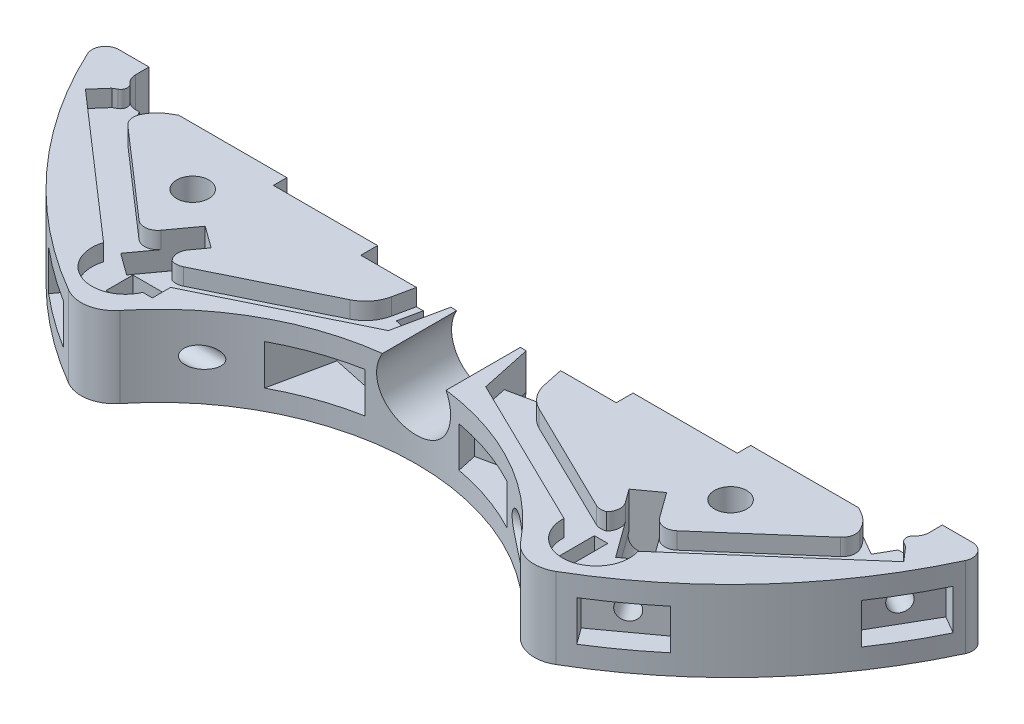
SolidWorks part; units mm, degrees
material "ABS"
ref_plane "Front Plane" through (0, 0, 0) normal (0, 0, 1) x (1, 0, 0)
ref_plane "Top Plane" through (0, 0, 0) normal (0, 1, 0) x (1, 0, 0)
ref_plane "Right Plane" through (0, 0, 0) normal (1, 0, 0) x (0, 0, -1)
sketch "Sketch1" plane through (0, 0, 0) normal (0, 1, 0) x (1, 0, 0)
  line L0 (0, -85) -> (-32.2211, -64.3879) construction
  line L1 (0, -85) -> (0, 0) construction
  arc A0 (36.2245, -62.2237) -> (-36.2245, -62.2237) centre (0, 0) ccw
  arc A1 (29.8119, -61.0352) -> (-29.8119, -61.0352) centre (0, -85) ccw
  arc A2 (36.2245, -62.2237) -> (29.8119, -61.0352) centre (33.7089, -57.9026) cw
  arc A3 (-29.8119, -61.0352) -> (-36.2245, -62.2237) centre (-33.7089, -57.9026) cw
  dimension "D1" = 144
  dimension "D2" = 76.5
  dimension "D4" = 5
  dimension "D3" = 85
extrude "Boss-Extrude1" add sketch "Sketch1" along normal mid plane 12
sketch "solenoid placement" plane through (0, 6, 0) normal (0, 1, 0) x (1, 0, 0)
  line L0 (0, 0) -> (0, -36) construction
  line L5 (-19, -36) -> (19, -36)
  line L7 (19, -36) -> (19, 28)
  line L9 (19, 28) -> (-19, 28)
  line L11 (-19, 28) -> (-19, -36)
  circle A1 centre (0, 0) radius 72 construction
  arc A2 (36.2245, -62.2237) -> (-36.2245, -62.2237) centre (0, 0) ccw construction
  point P7 (0, 28)
  dimension "D1" = 38
  dimension "D2" = 64
  dimension "D3" = 36
extrude "Cut-Extrude1" cut sketch "solenoid placement" against normal through all
sketch "Sketch6" plane through (0, 6, 0) normal (0, 1, 0) x (1, 0, 0)
  line L0 (0, 0) -> (0, -46.75) construction
  arc A0 (29.8119, -61.0352) -> (-29.8119, -61.0352) centre (0, -85) ccw construction
  circle A1 centre (40, -40) radius 2.4
  circle A4 centre (-40, -40) radius 2.4
  dimension "D1" = 4.8
  dimension "D2" = 40
  dimension "D3" = 40
extrude "Cut-Extrude6" cut sketch "Sketch6" against normal through all
sketch "Sketch3" plane through (0, 6, 0) normal (0, 1, 0) x (1, 0, 0)
  line L0 (-72, -27.5) -> (-59, -27.5)
  line L1 (-59, -31.5) -> (59, -31.5)
  line L2 (-72, -27.5) -> (-72, 31.5)
  line L3 (-59, -27.5) -> (-59, -31.5)
  line L4 (72, -27.5) -> (72, 31.5)
  line L5 (-72, 31.5) -> (72, 31.5) construction
  line L6 (0, 31.5) -> (0, -31.5) construction
  line L7 (59, -27.5) -> (59, -31.5)
  line L8 (-72, 31.5) -> (-72, 72)
  line L9 (72, -27.5) -> (59, -27.5)
  line L10 (-72, 72) -> (72, 72)
  line L11 (72, 31.5) -> (72, 72)
  arc A0 (36.2245, -62.2237) -> (-36.2245, -62.2237) centre (0, 0) ccw construction
  arc A1 (36.2245, -62.2237) -> (-36.2245, -62.2237) centre (0, 0) ccw construction
  point P0 (0, 0)
  dimension "D2" = 4
  dimension "D1" = 63
  dimension "D3" = 13
extrude "Cut-Extrude3" cut sketch "Sketch3" against normal through all
fillet "Fillet1" radius 2 4 edges at (66.5413, 0, 27.5) (59, 0, 31.5) (-66.5413, 0, 27.5) (-59, 0, 31.5)
sketch "Sketch8" plane through (0, 0, 0) normal (0, 1, 0) x (1, 0, 0)
  line L0 (0, 0) -> (62.3538, -36) construction
  line L1 (0, 0) -> (42.3205, -58.2492) construction
  line L2 (0, 0) -> (14.9696, -70.4266) construction
  line L3 (0, 0) -> (-14.9696, -70.4266) construction
  line L4 (-42.3205, -58.2492) -> (0, 0) construction
  line L5 (0, 0) -> (-62.3538, -36) construction
  line L6 (0, 0) -> (0, -72) construction
  arc A0 (-62.3538, -36) -> (-42.3205, -58.2492) centre (0, 0) ccw construction
  arc A1 (62.3538, -36) -> (42.3205, -58.2492) centre (0, 0) cw construction
  arc A2 (14.9696, -70.4266) -> (42.3205, -58.2492) centre (0, 0) ccw construction
  arc A3 (14.9696, -70.4266) -> (-14.9696, -70.4266) centre (0, 0) cw construction
  arc A4 (-14.9696, -70.4266) -> (-42.3205, -58.2492) centre (0, 0) cw construction
  arc A5 (36.2245, -62.2237) -> (65.294, -30.3429) centre (0, 0) ccw construction
  dimension "D1" = 120
sketch "Sketch9" plane through (0, 0, 0) normal (0, 1, 0) x (1, 0, 0)
  line L0 (0, 0) -> (-59.7033, -40.2432) construction
  line L1 (0, 0) -> (-64.7033, -31.583) construction
  line L2 (-64.7033, -31.583) -> (-59.7033, -40.2432) construction
  line L3 (-64.7033, -31.583) -> (-62.1052, -30.083)
  line L4 (-62.1052, -30.083) -> (-57.1052, -38.7432)
  line L5 (-57.1052, -38.7432) -> (-59.7033, -40.2432)
  line L6 (-46.2635, -55.1697) -> (-44.5001, -52.7426)
  line L7 (-44.5001, -52.7426) -> (-36.4099, -58.6205)
  line L8 (-36.4099, -58.6205) -> (-38.1733, -61.0475)
  line L9 (0, 0) -> (-38.1733, -61.0475) construction
  line L10 (0, 0) -> (-46.2635, -55.1697) construction
  line L11 (-46.2635, -55.1697) -> (-38.1733, -61.0475) construction
  line L12 (-19.8242, -69.217) -> (-19.2005, -66.2826) [skipped]
  line L13 (-19.2005, -66.2826) -> (-9.419, -68.3617) [skipped]
  line L14 (-9.419, -68.3617) -> (-10.0428, -71.2962) [skipped]
  line L15 (0, 0) -> (-10.0428, -71.2962) construction
  line L16 (0, 0) -> (-19.8242, -69.217) construction
  line L17 (-19.8242, -69.217) -> (-10.0428, -71.2962) construction
  line L18 (10.0428, -71.2962) -> (9.419, -68.3617) [skipped]
  line L19 (9.419, -68.3617) -> (19.2005, -66.2826) [skipped]
  line L20 (19.2005, -66.2826) -> (19.8242, -69.217) [skipped]
  line L21 (0, 0) -> (19.8242, -69.217) construction
  line L22 (0, 0) -> (10.0428, -71.2962) construction
  line L23 (10.0428, -71.2962) -> (19.8242, -69.217) construction
  line L24 (38.1733, -61.0475) -> (36.4099, -58.6205)
  line L25 (36.4099, -58.6205) -> (44.5001, -52.7426)
  line L26 (44.5001, -52.7426) -> (46.2635, -55.1697)
  line L27 (0, 0) -> (46.2635, -55.1697) construction
  line L28 (0, 0) -> (38.1733, -61.0475) construction
  line L29 (38.1733, -61.0475) -> (46.2635, -55.1697) construction
  line L30 (59.7033, -40.2432) -> (57.1052, -38.7432)
  line L31 (57.1052, -38.7432) -> (62.1052, -30.083)
  line L32 (62.1052, -30.083) -> (64.7033, -31.583)
  line L33 (0, 0) -> (64.7033, -31.583) construction
  line L34 (0, 0) -> (59.7033, -40.2432) construction
  line L35 (59.7033, -40.2432) -> (64.7033, -31.583) construction
  arc A0 (-59.7033, -40.2432) -> (-64.7033, -31.583) centre (0, 0) cw
  arc A1 (-62.3538, -36) -> (-42.3205, -58.2492) centre (0, 0) ccw construction
  arc A2 (-38.1733, -61.0475) -> (-46.2635, -55.1697) centre (0, 0) cw
  arc A3 (-10.0428, -71.2962) -> (-19.8242, -69.217) centre (0, 0) cw [skipped]
  arc A4 (19.8242, -69.217) -> (10.0428, -71.2962) centre (0, 0) cw [skipped]
  arc A5 (46.2635, -55.1697) -> (38.1733, -61.0475) centre (0, 0) cw
  arc A6 (64.7033, -31.583) -> (59.7033, -40.2432) centre (0, 0) cw
  point P8 (-62.3538, -36)
  point P12 (62.3538, -36)
  point P34 (0, 0)
  dimension "D1" = 10
  dimension "D2" = 3
  dimension "D3" = 6
extrude "Cut-Extrude7" cut sketch "Sketch9" against normal mid plane 6
sketch "Sketch11" plane through (0, 0, 36) normal (0, 0, -1) x (-1, 0, 0)
  line L0 (0, -6) -> (0, 3.2) construction
  line L1 (19, -6) -> (-19, -6) construction
  circle A0 centre (0, 3.2) radius 5.5
  dimension "D2" = 11
  dimension "D1" = 9.2
extrude "Cut-Extrude8" cut sketch "Sketch11" against normal through all
sketch "Sketch12" plane through (0, 6, 0) normal (0, 1, 0) x (1, 0, 0)
  line L1 (-34.5, 33.5) -> (34.5, 33.5)
  line L2 (-34.5, 33.5) -> (-34.5, -33.5)
  line L3 (-34.5, -33.5) -> (34.5, -33.5)
  line L4 (34.5, 33.5) -> (34.5, -33.5)
  line L5 (-34.5, 33.5) -> (34.5, -33.5) construction
  line L6 (-34.5, -33.5) -> (34.5, 33.5) construction
  point P0 (0, 0)
  dimension "D1" = 69
  dimension "D2" = 67
extrude "Cut-Extrude9" cut sketch "Sketch12" against normal through all
sketch "Sketch13" plane through (0, 6, 0) normal (0, 1, 0) x (1, 0, 0)
  line L0 (0, 0) -> (0, -97.3817) construction
  circle A0 centre (-35, -55) radius 5
  circle A1 centre (35, -55) radius 5
  dimension "D3" = 10
  dimension "D1" = 35
  dimension "D2" = 55
extrude "Cut-Extrude10" cut sketch "Sketch13" against normal blind 2.5
sketch "Sketch14" plane through (0, 0, 0) normal (0, 1, 0) x (1, 0, 0)
  line L0 (16.1653, -42.3838) -> (6.3839, -44.463)
  line L1 (16.1653, -42.3838) -> (16.7891, -45.3183)
  line L2 (6.3839, -44.463) -> (7.0076, -47.3974)
  line L3 (16.7891, -45.3183) -> (7.0076, -47.3974) construction
  line L4 (0, 0) -> (14.9696, -70.4266) construction
  line L5 (16.7891, -45.3183) -> (7.0076, -47.3974) construction
  line L6 (16.7891, -45.3183) -> (18.0563, -51.2801)
  line L7 (7.0076, -47.3974) -> (8.2748, -53.3592)
  line L8 (18.0563, -51.2801) -> (8.2748, -53.3592)
  line L9 (0, 0) -> (0, -72) construction
  line L10 (-16.7891, -45.3183) -> (-7.0076, -47.3974) construction
  line L11 (-16.7891, -45.3183) -> (-7.0076, -47.3974) construction
  line L12 (-18.0563, -51.2801) -> (-8.2748, -53.3592)
  line L13 (-7.0076, -47.3974) -> (-8.2748, -53.3592)
  line L14 (-16.7891, -45.3183) -> (-18.0563, -51.2801)
  line L15 (-6.3839, -44.463) -> (-7.0076, -47.3974)
  line L16 (-16.1653, -42.3838) -> (-16.7891, -45.3183)
  line L17 (-16.1653, -42.3838) -> (-6.3839, -44.463)
  arc A0 (29.8119, -61.0352) -> (4.7339, -47.0441) centre (0, -85) ccw construction
  dimension "D1" = 10
  dimension "D2" = 3
  dimension "D3" = 3
extrude "Cut-Extrude11" cut sketch "Sketch14" against normal mid plane 6
sketch "Sketch15" plane through (59.6052, 0, 34.4131) normal (0.866, 0, 0.5) x (0.5, 0, -0.866)
  circle A0 centre (0, 0) radius 1.55
  dimension "D1" = 3.1
extrude "Cut-Extrude12" cut sketch "Sketch15" against normal blind 4.2
sketch "Sketch16" plane through (55.9679, 0, 32.3131) normal (0.866, 0, 0.5) x (0.5, 0, -0.866)
  circle A0 centre (0, 0) radius 2.1
  dimension "D1" = 4.2
extrude "Cut-Extrude13" cut sketch "Sketch16" against normal blind 9
sketch "Sketch17" plane through (55.9679, 0, 32.3131) normal (-0.866, 0, -0.5) x (-0.5, 0, 0.866)
  line L1 (-2, 0) -> (2, 0)
  line L2 (-2, 0) -> (-2, 7.9151)
  line L3 (-2, 7.9151) -> (2, 7.9151)
  line L4 (2, 0) -> (2, 7.9151)
  point P0 (0, 0)
  dimension "D1" = 4
extrude "Cut-Extrude14" cut sketch "Sketch17" along normal blind 9
pattern_circular "CirPattern1" count 6 over 120 about axis through (0, 6, 0) along (0, -1, 0) of "Cut-Extrude12", "Cut-Extrude13", "Cut-Extrude14"
sketch "Sketch18" plane through (9.3183, 0, 43.8392) normal (0.2079, 0, 0.9781) x (0.9781, 0, -0.2079)
  circle A0 centre (0, 0) radius 1.55
  dimension "D1" = 3.1
extrude "Cut-Extrude15" cut sketch "Sketch18" against normal blind 4.2
sketch "Sketch19" plane through (8.4451, 0, 39.731) normal (0.2079, 0, 0.9781) x (0.9781, 0, -0.2079)
  circle A0 centre (0, 0) radius 2.1
  dimension "D1" = 4.2
extrude "Cut-Extrude16" cut sketch "Sketch19" against normal blind 9
sketch "Sketch20" plane through (8.4451, 0, 39.731) normal (-0.2079, 0, -0.9781) x (-0.9781, 0, 0.2079)
  line L1 (-2, 0) -> (2, 0)
  line L2 (-2, 0) -> (-2, 10.352)
  line L3 (-2, 10.352) -> (2, 10.352)
  line L4 (2, 0) -> (2, 10.352)
  point P0 (0, 0)
  dimension "D1" = 4
extrude "Cut-Extrude17" cut sketch "Sketch20" along normal blind 9
pattern_circular "CirPattern2" count 2 over 24 about axis through (0, 6, 0) along (0, -1, 0) of "Cut-Extrude15", "Cut-Extrude16", "Cut-Extrude17"
sketch "Sketch21" plane through (0, 6, 0) normal (0, 1, 0) x (1, 0, 0)
  line L0 (10.4981, -34.9604) -> (5.6074, -36)
  line L1 (5.6074, -36) -> (7.1125, -43.0813)
  line L2 (7.1125, -43.0813) -> (12.0033, -42.0417) construction
  line L3 (11.8821, -41.4715) -> (10.4981, -34.9604)
  line L4 (35, -55) -> (59.5494, -33.5894) construction
  line L5 (53.9374, -35.8301) -> (56.4374, -31.5)
  line L6 (56.4374, -31.5) -> (59.0354, -33)
  line L8 (-12.0033, -42.0417) -> (-11.8821, -41.4715) construction
  line L9 (-9.5579, -42.5615) -> (-35, -55) construction
  line L10 (-35, -55) -> (-59.5494, -33.5894) construction
  line L11 (56.4374, -31.5) -> (54.9679, -34.0451) construction
  line L13 (9.5579, -42.5615) -> (35, -55) construction
  line L14 (36.3146, -56.5073) -> (60.864, -35.0966)
  line L15 (34.6859, -52.6202) -> (53.9374, -35.8301)
  line L16 (7.2337, -43.6514) -> (34.1216, -56.7968)
  line L17 (11.8821, -41.4715) -> (34.6859, -52.6202)
  line L18 (60.864, -35.0966) -> (59.0354, -33)
  line L19 (7.2337, -43.6514) -> (7.1125, -43.0813)
  line L20 (36.3146, -56.5073) -> (34.1216, -56.7968)
  line L21 (33.6854, -53.4927) -> (58.2349, -32.0821) construction
  line L22 (8.9906, -40.0579) -> (35.8784, -53.2032) construction
  line L23 (12.0033, -42.0417) -> (11.8821, -41.4715) construction
  line L24 (8.1121, -41.8547) -> (35, -55) construction
  line L25 (-7.1125, -43.0813) -> (-12.0033, -42.0417) construction
  line L26 (35, -55) -> (59.5494, -33.5894) construction
  line L27 (0, 0) -> (0, -87.81) construction
  line L28 (-36.3146, -56.5073) -> (-34.1216, -56.7968)
  line L29 (-7.2337, -43.6514) -> (-7.1125, -43.0813)
  line L30 (-60.864, -35.0966) -> (-59.0354, -33)
  line L31 (-11.8821, -41.4715) -> (-34.6859, -52.6202)
  line L32 (-7.2337, -43.6514) -> (-34.1216, -56.7968)
  line L33 (-34.6859, -52.6202) -> (-53.9374, -35.8301)
  line L34 (-36.3146, -56.5073) -> (-60.864, -35.0966)
  line L35 (-56.4374, -31.5) -> (-59.0354, -33)
  line L36 (-53.9374, -35.8301) -> (-56.4374, -31.5)
  line L37 (-11.8821, -41.4715) -> (-10.4981, -34.9604)
  line L38 (-5.6074, -36) -> (-7.1125, -43.0813)
  line L39 (-10.4981, -34.9604) -> (-5.6074, -36)
  line L40 (5.6074, -36) -> (6.4888, -40.1468) construction
  line L41 (10.4014, -39.3152) -> (6.4888, -40.1468) construction
  point P2 (0, 0)
  point P5 (58.0966, -34.6262)
  point P6 (0, 0)
  point P8 (54.4304, -34.8417)
  point P14 (54.4392, -34.9609)
  point P15 (57.387, -35.8551)
  point P17 (0, 0)
  point P22 (0, 0)
  point P23 (56.6968, -37.0506)
  point P36 (0, 0)
  point P37 (0, 0)
  point P40 (59.5494, -33.5894)
  point P43 (61.5975, -36.1875)
  point P44 (0, 0)
  point P45 (11.5836, -39.3746)
  point P46 (10.8581, -37.7159)
  point P47 (0, 0)
  point P48 (0, 0)
  point P49 (53.9374, -35.9023)
  point P58 (59.4282, -32.3197)
  point P59 (0, 0)
  point P60 (58.2331, -34.3896)
  point P61 (57.3367, -35.9423)
  point P62 (56.4374, -31.5)
  point P64 (0, 0)
  point P65 (56.6327, -33.781)
  point P66 (0, 0)
  point P74 (0, 0)
  point P75 (0, 0)
  point P76 (0, 0)
  point P78 (5.6074, -36)
  point P80 (6.4873, -38.883)
  point P81 (7.1876, -43.3783)
  point P82 (10.3917, -34.5734)
  point P85 (7.0831, -42.4103)
  dimension "D1" = 3
  dimension "D2" = 2
  dimension "D6" = 5
  dimension "D7" = 5
  dimension "D8" = 3
  dimension "D3" = 2
  dimension "D4" = 2
  dimension "D5" = 2
extrude "Cut-Extrude19" cut sketch "Sketch21" against normal blind 2.5
sketch "Sketch22" plane through (0, 0, 0) normal (1, 0, 0) x (0, 0, -1)
  line L0 (-55, 0) -> (0, 0) construction
  circle A0 centre (-55, 0) radius 1.55
  dimension "D1" = 3.1
  dimension "D2" = 55
extrude "Cut-Extrude20" cut sketch "Sketch22" against normal blind 29
sketch "Sketch23" plane through (-29, 0, 0) normal (1, 0, 0) x (0, 0, -1)
  line L0 (-55, 0) -> (-55, 8.7926) construction
  line L1 (-57, 8.7926) -> (-53, 8.7926)
  line L2 (-57, 8.7926) -> (-57, 0.6403)
  line L4 (-53, 8.7926) -> (-53, 0.6403)
  arc A0 (-57, 0.6403) -> (-53, 0.6403) centre (-55, 0) ccw
  dimension "D1" = 4.2
  dimension "D2" = 4
extrude "Cut-Extrude21" cut sketch "Sketch23" against normal blind 6.9
sketch "Sketch24" plane through (0, 0, 0) normal (1, 0, 0) x (0, 0, -1)
  circle A0 centre (-55, 0) radius 2.75
  circle A1 centre (-55, 0) radius 1.55 construction
  dimension "D1" = 5.5
extrude "Cut-Extrude23" cut sketch "Sketch24" along normal blind 30
sketch "Sketch25" plane through (30, 0, 0) normal (-1, 0, 0) x (0, 0, 1)
  line L1 (52.25, 0.5) -> (57.75, 0.5)
  line L2 (52.25, 0.5) -> (52.25, -0.5)
  line L3 (52.25, -0.5) -> (57.75, -0.5)
  line L4 (57.75, 0.5) -> (57.75, -0.5)
  line L5 (52.25, 0.5) -> (57.75, -0.5) construction
  line L6 (52.25, -0.5) -> (57.75, 0.5) construction
  circle A0 centre (55, 0) radius 2.75 construction
  point P0 (55, 0)
  dimension "D1" = 1
extrude "Cut-Extrude24" cut sketch "Sketch25" against normal blind 4
sketch "Sketch26" plane through (0, 0.5, 0) normal (0, -1, 0) x (1, 0, 0)
  line L1 (34, 52.25) -> (32, 52.25)
  line L2 (34, 52.25) -> (34, 57.75)
  line L3 (34, 57.75) -> (32, 57.75)
  line L4 (32, 52.25) -> (32, 57.75)
  dimension "D1" = 2
extrude "Cut-Extrude25" cut sketch "Sketch26" against normal through all
fillet "Fillet5" radius 5 2 edges at (-54.9679, 4.75, 34.0451) (54.9679, 4.75, 34.0451)
fillet "Fillet7" radius 2 2 edges at (53.9374, 4.75, 35.8301) (-53.9374, 4.75, 35.8301)
sketch "Sketch28" plane through (0, 6, 0) normal (0, 1, 0) x (1, 0, 0)
  line L0 (59.0354, -33) -> (56.4374, -31.5) construction
  line L1 (58.2925, -31.0263) -> (56.4374, -31.5)
  line L2 (56.4374, -31.5) -> (58.4387, -32.6555)
  line L3 (0, 0) -> (0, -21.6365) construction
  line L4 (-56.4374, -31.5) -> (-58.4387, -32.6555)
  line L5 (-58.2925, -31.0263) -> (-56.4374, -31.5)
  arc A0 (58.2925, -31.0263) -> (58.4387, -32.6555) centre (58.9387, -31.7894) ccw
  arc A1 (57, -31.5) -> (59, -29.5) centre (57, -29.5) ccw construction
  arc A2 (-58.2925, -31.0263) -> (-58.4387, -32.6555) centre (-58.9387, -31.7894) cw
  dimension "D1" = 2
extrude "Cut-Extrude26" cut sketch "Sketch28" against normal up to surface (2.5 mm away) up to face at (-34.4967, 3.5, 44.1866)
fillet "Fillet10" radius 5 2 edges at (-11.8821, 4.75, 41.4715) (11.8821, 4.75, 41.4715)
fillet "Fillet11" radius 2 3 edges at (31.7615, 4.75, 51.1905) (33.9379, 4.75, 50.1141) (38.3691, 4.75, 49.4079)
fillet "Fillet12" radius 2 3 edges at (-31.7615, 4.75, 51.1905) (-33.9379, 4.75, 50.1141) (-38.3691, 4.75, 49.4079)
equation "\"smallPulleyTeeth\"= 30"
equation "\"largePulleyTeeth\"= 30"
equation "\"eighthThick\"= 3.0mm"
equation "\"sixteenthThick\" = 1.7mm"
equation "\"quarterThick\"=6.0mm"
equation "\"OD\" = 145mm"
equation "\"puckAngle\" = 60.5deg"
equation "\"puckDiam\" = 76.5mm"
equation "\"D2@Sketch1\"=\"puckDiam\""
equation "\"D1@Boss-Extrude1\"=\"eighthThick\"*4"
equation "\"axlePress\" = 5.9mm"
equation "\"press\" = 0.2mm"
equation "\"wheelClear\" = 0.3mm"
equation "\"10-32clear\" = 4.8mm"
equation "\"6-32clear\" = 3.3mm"
equation "\"8-32clear\" = 4.0mm"
equation "\"wheelHeight\" = 22mm"
equation "\"wheelWell\" = 65mm"
equation "\"puckDist\" = 85mm"
equation "\"scoopFillet\" = 5mm"
equation "\"4-40clear\" = 3.0mm"
equation "\"D3@Sketch1\"=\"puckDist\""
equation "\"D4@Sketch1\"=\"scoopFillet\""
equation "\"D1@Sketch6\"=\"10-32clear\""
equation "\"D2@Sketch9\"=\"eighthThick\""
equation "\"D2@Sketch14\"=\"eighthThick\""
equation "\"10-32tap\" = 4.45mm"
equation "\"ledSmall\" = 3.1mm"
equation "\"ledLarge\" = 4.2mm"
equation "\"ledLength\" = 4.2mm"
equation "\"D1@Cut-Extrude12\"=\"ledLength\""
equation "\"D1@Sketch15\"=\"ledSmall\""
equation "\"D1@Sketch16\"=\"ledLarge\""
equation "\"D1@Sketch18\"=\"ledSmall\""
equation "\"D1@Cut-Extrude15\"=\"ledLength\""
equation "\"D1@Sketch19\"=\"ledLarge\""
equation "\"D1@Sketch23\"=\"ledLarge\""
